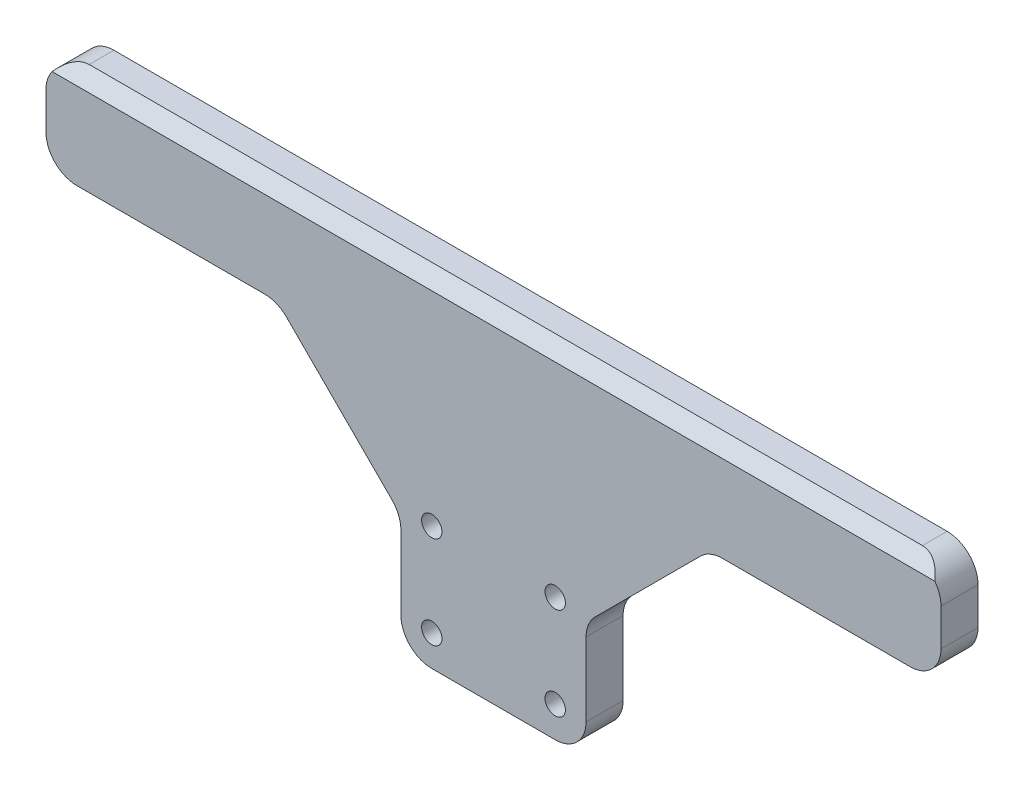
SolidWorks part; units mm, degrees
ref_plane "Front" through (0, 0, 0) normal (0, 0, 1) x (1, 0, 0)
ref_plane "Top" through (0, 0, 0) normal (0, 1, 0) x (1, 0, 0)
ref_plane "Right" through (0, 0, 0) normal (1, 0, 0) x (0, 0, -1)
sketch "Esquisse1" plane through (0, 0, 0) normal (0, 0, 1) x (1, 0, 0)
  line L1 (0, 0) -> (145, 0)
  line L2 (0, 0) -> (0, 25)
  line L3 (0, 25) -> (145, 25)
  line L4 (145, 0) -> (145, 25)
  dimension "D1" = 145
  dimension "D2" = 25
extrude "Boss.-Extru.1" add sketch "Esquisse1" along normal blind 6
sketch "Esquisse2" plane through (0, 0, 6) normal (0, 0, 1) x (1, 0, 0)
  line L0 (72.5, 0) -> (72.5, 25) construction
  line L1 (0, 0) -> (145, 0) construction
  line L2 (145, 25) -> (0, 25) construction
  line L3 (72.5, 12.5) -> (26.2893, 12.5) construction
  circle A0 centre (62.5, 20) radius 1.65
  circle A1 centre (62.5, 5) radius 1.65
  circle A2 centre (82.5, 5) radius 1.65
  circle A3 centre (82.5, 20) radius 1.65
  dimension "D1" = 20
  dimension "D2" = 15
  dimension "D3" = 3.3
extrude "Enlèv. mat.-Extru.1" cut sketch "Esquisse2" against normal through all both and the other way through all
sketch "Esquisse3" plane through (0, 0, 6) normal (0, 0, 1) x (1, 0, 0)
  line L0 (145, 0) -> (145, 25) construction
  line L1 (0, 25) -> (145, 25)
  line L2 (0, 25) -> (0, 55)
  line L3 (0, 55) -> (145, 55)
  line L4 (145, 25) -> (145, 55)
  dimension "D1" = 30
extrude "Boss.-Extru.2" add sketch "Esquisse3" against normal up to vertex (6 mm away) up to point (145, 25, 0)
chamfer "Chanfrein1" distance 2 angle 45 1 edges at (72.5, 55, 6)
sketch "Esquisse4" plane through (0, 0, 6) normal (0, 0, 1) x (1, 0, 0)
  line L0 (72.5, 0) -> (72.5, 55) construction
  line L1 (0, 0) -> (57.5, 0)
  line L2 (0, 0) -> (0, 39)
  line L3 (0, 39) -> (57.5, 39)
  line L4 (57.5, 0) -> (57.5, 39)
  line L5 (0, 0) -> (145, 0) construction
  line L6 (0, 55) -> (145, 55) construction
  line L7 (87.5, 0) -> (87.5, 39)
  line L8 (145, 39) -> (87.5, 39)
  line L9 (145, 0) -> (145, 39)
  line L10 (145, 0) -> (87.5, 0)
  dimension "D1" = 30
  dimension "D2" = 16
extrude "Enlèv. mat.-Extru.2" cut sketch "Esquisse4" against normal through all both and the other way through all
chamfer "Chanfrein2" distance 20 angle 45 2 edges at (87.5, 39, 3) (57.5, 39, 3)
fillet "Congé2" radius 5 10 edges at (145, 55, 2) (145, 39, 3) (107.5, 39, 3) (87.5, 19, 3) (87.5, 0, 3) (57.5, 0, 3) (57.5, 19, 3) (37.5, 39, 3) (0, 39, 3) (0, 55, 2)
